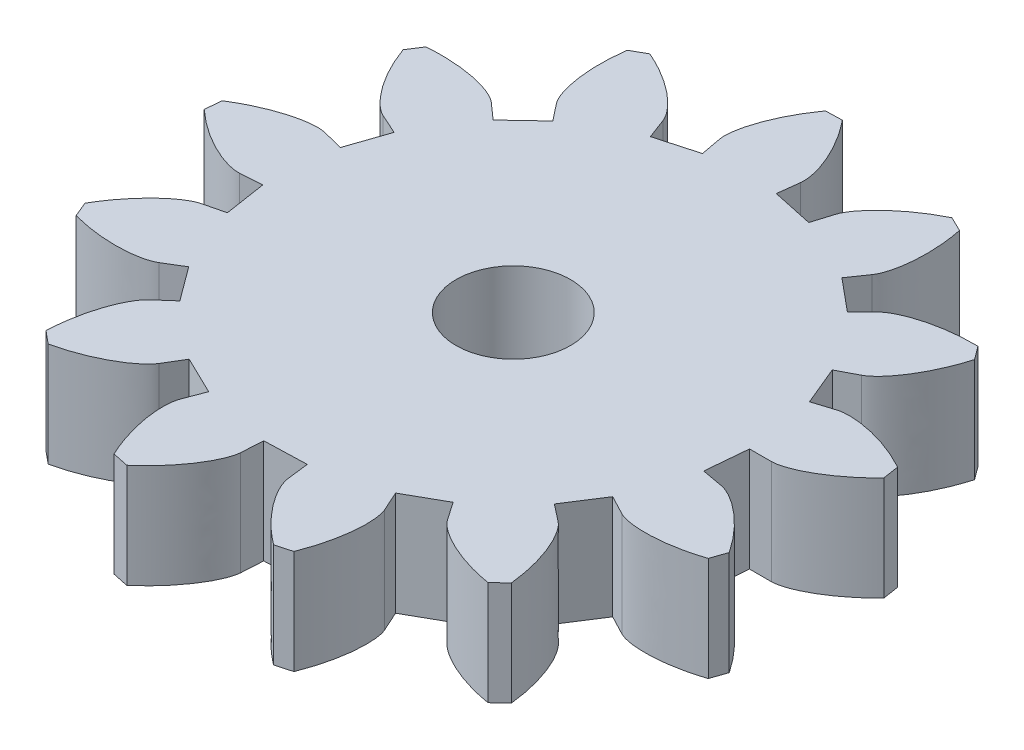
SolidWorks part; units mm, degrees
ref_plane "Front Plane" through (0, 0, 0) normal (0, 0, 1) x (1, 0, 0)
ref_plane "Top Plane" through (0, 0, 0) normal (0, 1, 0) x (1, 0, 0)
ref_plane "Right Plane" through (0, 0, 0) normal (1, 0, 0) x (0, 0, -1)
sketch "Sketch1" plane through (0, 0, 0) normal (0, 1, 0) x (1, 0, 0)
  circle A0 centre (0, 0) radius 8.2743 construction
  circle A1 centre (0, 0) radius 8.2743
sketch "Sketch2" plane through (0, 0, 0) normal (0, 1, 0) x (1, 0, 0)
  line L0 (6.8098, 0) -> (7.4374, 0)
  line L1 (7.4374, 0) -> (7.4435, 0.0002)
  line L2 (7.4435, 0.0002) -> (7.455, 0.0009)
  line L3 (7.455, 0.0009) -> (7.4719, 0.0023)
  line L4 (7.4719, 0.0023) -> (7.494, 0.0048)
  line L5 (7.494, 0.0048) -> (7.5213, 0.0086)
  line L6 (7.5213, 0.0086) -> (7.5538, 0.0141)
  line L7 (7.5538, 0.0141) -> (7.5915, 0.0214)
  line L8 (7.5915, 0.0214) -> (7.6341, 0.0309)
  line L9 (7.6341, 0.0309) -> (7.6817, 0.0428)
  line L10 (7.6817, 0.0428) -> (7.7341, 0.0575)
  line L11 (7.7341, 0.0575) -> (7.7912, 0.0751)
  line L12 (7.7912, 0.0751) -> (7.8529, 0.096)
  line L13 (7.8529, 0.096) -> (7.9191, 0.1204)
  line L14 (7.9191, 0.1204) -> (7.9895, 0.1486)
  line L15 (7.9895, 0.1486) -> (8.0641, 0.1807)
  line L16 (8.0641, 0.1807) -> (8.1427, 0.2171)
  line L17 (8.1427, 0.2171) -> (8.225, 0.258)
  line L18 (8.225, 0.258) -> (8.311, 0.3036)
  line L19 (8.311, 0.3036) -> (8.4004, 0.3541)
  line L20 (8.4004, 0.3541) -> (8.493, 0.4097)
  line L21 (8.493, 0.4097) -> (8.5886, 0.4707)
  line L22 (8.5886, 0.4707) -> (8.6869, 0.5373)
  line L23 (8.6869, 0.5373) -> (8.7878, 0.6095)
  line L24 (8.7878, 0.6095) -> (8.891, 0.6877)
  line L25 (8.891, 0.6877) -> (8.9962, 0.772)
  line L26 (8.9962, 0.772) -> (9.1033, 0.8626)
  line L27 (9.1033, 0.8626) -> (9.2118, 0.9596)
  line L28 (9.2118, 0.9596) -> (9.3216, 1.0631)
  line L29 (9.3216, 1.0631) -> (9.4324, 1.1733)
  line L30 (9.4324, 1.1733) -> (9.4602, 1.2019)
  line L31 (9.4602, 1.2019) -> (9.4672, 1.2092)
  line L32 (9.4672, 1.2092) -> (9.4689, 1.211)
  line L33 (9.4689, 1.211) -> (9.4692, 1.2112)
  line L34 (9.4692, 1.2112) -> (9.4693, 1.2114)
  line L35 (9.4693, 1.2114) -> (9.3971, 1.6821)
  line L36 (9.3971, 1.6821) -> (9.3969, 1.6823)
  line L37 (9.3969, 1.6823) -> (9.3966, 1.6825)
  line L38 (9.3966, 1.6825) -> (9.3944, 1.6837)
  line L39 (9.3944, 1.6837) -> (9.3856, 1.6885)
  line L40 (9.3856, 1.6885) -> (9.3505, 1.7074)
  line L41 (9.3505, 1.7074) -> (9.2118, 1.7794)
  line L42 (9.2118, 1.7794) -> (9.076, 1.8452)
  line L43 (9.076, 1.8452) -> (8.9434, 1.9052)
  line L44 (8.9434, 1.9052) -> (8.8141, 1.9595)
  line L45 (8.8141, 1.9595) -> (8.6884, 2.0084)
  line L46 (8.6884, 2.0084) -> (8.5666, 2.0521)
  line L47 (8.5666, 2.0521) -> (8.4487, 2.0908)
  line L48 (8.4487, 2.0908) -> (8.3349, 2.1248)
  line L49 (8.3349, 2.1248) -> (8.2254, 2.1544)
  line L50 (8.2254, 2.1544) -> (8.1204, 2.1797)
  line L51 (8.1204, 2.1797) -> (8.02, 2.2011)
  line L52 (8.02, 2.2011) -> (7.9243, 2.2189)
  line L53 (7.9243, 2.2189) -> (7.8335, 2.2332)
  line L54 (7.8335, 2.2332) -> (7.7476, 2.2443)
  line L55 (7.7476, 2.2443) -> (7.6668, 2.2527)
  line L56 (7.6668, 2.2527) -> (7.5912, 2.2584)
  line L57 (7.5912, 2.2584) -> (7.5207, 2.2618)
  line L58 (7.5207, 2.2618) -> (7.4556, 2.2633)
  line L59 (7.4556, 2.2633) -> (7.3958, 2.263)
  line L60 (7.3958, 2.263) -> (7.3415, 2.2613)
  line L61 (7.3415, 2.2613) -> (7.2925, 2.2584)
  line L62 (7.2925, 2.2584) -> (7.2489, 2.2547)
  line L63 (7.2489, 2.2547) -> (7.2109, 2.2504)
  line L64 (7.2109, 2.2504) -> (7.1782, 2.2458)
  line L65 (7.1782, 2.2458) -> (7.151, 2.2413)
  line L66 (7.151, 2.2413) -> (7.1291, 2.237)
  line L67 (7.1291, 2.237) -> (7.1126, 2.2334)
  line L68 (7.1126, 2.2334) -> (7.1015, 2.2306)
  line L69 (7.1015, 2.2306) -> (7.0955, 2.2289)
  line L70 (7.0955, 2.2289) -> (6.4968, 2.0408)
  line L71 (6.4968, 2.0408) -> (6.0298, 3.1647)
  line L72 (6.0298, 3.1647) -> (6.5855, 3.4563)
  line L73 (6.5855, 3.4563) -> (6.5908, 3.4594)
  line L74 (6.5908, 3.4594) -> (6.6007, 3.4653)
  line L75 (6.6007, 3.4653) -> (6.6149, 3.4744)
  line L76 (6.6149, 3.4744) -> (6.6333, 3.4869)
  line L77 (6.6333, 3.4869) -> (6.6558, 3.503)
  line L78 (6.6558, 3.503) -> (6.6821, 3.5229)
  line L79 (6.6821, 3.5229) -> (6.712, 3.5469)
  line L80 (6.712, 3.5469) -> (6.7453, 3.5751)
  line L81 (6.7453, 3.5751) -> (6.7819, 3.6078)
  line L82 (6.7819, 3.6078) -> (6.8215, 3.6451)
  line L83 (6.8215, 3.6451) -> (6.8639, 3.6873)
  line L84 (6.8639, 3.6873) -> (6.9088, 3.7345)
  line L85 (6.9088, 3.7345) -> (6.956, 3.7868)
  line L86 (6.956, 3.7868) -> (7.0053, 3.8445)
  line L87 (7.0053, 3.8445) -> (7.0564, 3.9076)
  line L88 (7.0564, 3.9076) -> (7.1091, 3.9763)
  line L89 (7.1091, 3.9763) -> (7.163, 4.0508)
  line L90 (7.163, 4.0508) -> (7.218, 4.1311)
  line L91 (7.218, 4.1311) -> (7.2736, 4.2174)
  line L92 (7.2736, 4.2174) -> (7.3298, 4.3097)
  line L93 (7.3298, 4.3097) -> (7.3861, 4.4081)
  line L94 (7.3861, 4.4081) -> (7.4422, 4.5127)
  line L95 (7.4422, 4.5127) -> (7.498, 4.6236)
  line L96 (7.498, 4.6236) -> (7.553, 4.7408)
  line L97 (7.553, 4.7408) -> (7.607, 4.8644)
  line L98 (7.607, 4.8644) -> (7.6597, 4.9943)
  line L99 (7.6597, 4.9943) -> (7.7107, 5.1306)
  line L100 (7.7107, 5.1306) -> (7.7598, 5.2733)
  line L101 (7.7598, 5.2733) -> (7.8067, 5.4224)
  line L102 (7.8067, 5.4224) -> (7.8181, 5.4607)
  line L103 (7.8181, 5.4607) -> (7.8209, 5.4703)
  line L104 (7.8209, 5.4703) -> (7.8216, 5.4727)
  line L105 (7.8216, 5.4727) -> (7.8217, 5.473)
  line L106 (7.8217, 5.473) -> (7.8216, 5.4732)
  line L107 (7.8216, 5.4732) -> (7.539, 5.8565)
  line L108 (7.539, 5.8565) -> (7.5387, 5.8566)
  line L109 (7.5387, 5.8566) -> (7.5384, 5.8566)
  line L110 (7.5384, 5.8566) -> (7.5359, 5.8566)
  line L111 (7.5359, 5.8566) -> (7.5259, 5.8568)
  line L112 (7.5259, 5.8568) -> (7.486, 5.8572)
  line L113 (7.486, 5.8572) -> (7.3297, 5.8565)
  line L114 (7.3297, 5.8565) -> (7.1789, 5.8517)
  line L115 (7.1789, 5.8517) -> (7.0336, 5.8432)
  line L116 (7.0336, 5.8432) -> (6.8939, 5.8312)
  line L117 (6.8939, 5.8312) -> (6.7599, 5.8161)
  line L118 (6.7599, 5.8161) -> (6.6317, 5.7981)
  line L119 (6.6317, 5.7981) -> (6.5093, 5.7776)
  line L120 (6.5093, 5.7776) -> (6.3927, 5.7549)
  line L121 (6.3927, 5.7549) -> (6.282, 5.7302)
  line L122 (6.282, 5.7302) -> (6.1773, 5.7038)
  line L123 (6.1773, 5.7038) -> (6.0784, 5.6761)
  line L124 (6.0784, 5.6761) -> (5.9855, 5.6473)
  line L125 (5.9855, 5.6473) -> (5.8984, 5.6178)
  line L126 (5.8984, 5.6178) -> (5.8172, 5.5878)
  line L127 (5.8172, 5.5878) -> (5.7418, 5.5576)
  line L128 (5.7418, 5.5576) -> (5.6721, 5.5275)
  line L129 (5.6721, 5.5275) -> (5.6082, 5.4978)
  line L130 (5.6082, 5.4978) -> (5.5498, 5.4688)
  line L131 (5.5498, 5.4688) -> (5.497, 5.4408)
  line L132 (5.497, 5.4408) -> (5.4497, 5.414)
  line L133 (5.4497, 5.414) -> (5.4076, 5.3887)
  line L134 (5.4076, 5.3887) -> (5.3708, 5.3652)
  line L135 (5.3708, 5.3652) -> (5.3391, 5.3437)
  line L136 (5.3391, 5.3437) -> (5.3123, 5.3245)
  line L137 (5.3123, 5.3245) -> (5.2903, 5.3078)
  line L138 (5.2903, 5.3078) -> (5.2729, 5.2939)
  line L139 (5.2729, 5.2939) -> (5.26, 5.283)
  line L140 (5.26, 5.283) -> (5.2514, 5.2753)
  line L141 (5.2514, 5.2753) -> (5.247, 5.2711)
  line L142 (5.247, 5.2711) -> (4.8042, 4.8263)
  line L143 (4.8042, 4.8263) -> (3.8684, 5.6043)
  line L144 (3.8684, 5.6043) -> (4.2249, 6.1208)
  line L145 (4.2249, 6.1208) -> (4.2282, 6.126)
  line L146 (4.2282, 6.126) -> (4.2342, 6.1359)
  line L147 (4.2342, 6.1359) -> (4.2426, 6.1505)
  line L148 (4.2426, 6.1505) -> (4.2531, 6.1702)
  line L149 (4.2531, 6.1702) -> (4.2655, 6.1948)
  line L150 (4.2655, 6.1948) -> (4.2795, 6.2247)
  line L151 (4.2795, 6.2247) -> (4.2948, 6.2598)
  line L152 (4.2948, 6.2598) -> (4.3112, 6.3003)
  line L153 (4.3112, 6.3003) -> (4.3284, 6.3462)
  line L154 (4.3284, 6.3462) -> (4.3462, 6.3977)
  line L155 (4.3462, 6.3977) -> (4.3641, 6.4547)
  line L156 (4.3641, 6.4547) -> (4.3819, 6.5174)
  line L157 (4.3819, 6.5174) -> (4.3994, 6.5857)
  line L158 (4.3994, 6.5857) -> (4.4163, 6.6596)
  line L159 (4.4163, 6.6596) -> (4.4322, 6.7393)
  line L160 (4.4322, 6.7393) -> (4.4469, 6.8246)
  line L161 (4.4469, 6.8246) -> (4.46, 6.9156)
  line L162 (4.46, 6.9156) -> (4.4714, 7.0123)
  line L163 (4.4714, 7.0123) -> (4.4806, 7.1145)
  line L164 (4.4806, 7.1145) -> (4.4874, 7.2223)
  line L165 (4.4874, 7.2223) -> (4.4915, 7.3356)
  line L166 (4.4915, 7.3356) -> (4.4926, 7.4544)
  line L167 (4.4926, 7.4544) -> (4.4904, 7.5785)
  line L168 (4.4904, 7.5785) -> (4.4847, 7.7078)
  line L169 (4.4847, 7.7078) -> (4.4751, 7.8423)
  line L170 (4.4751, 7.8423) -> (4.4613, 7.9819)
  line L171 (4.4613, 7.9819) -> (4.4432, 8.1263)
  line L172 (4.4432, 8.1263) -> (4.4204, 8.2755)
  line L173 (4.4204, 8.2755) -> (4.3926, 8.4293)
  line L174 (4.3926, 8.4293) -> (4.3849, 8.4684)
  line L175 (4.3849, 8.4684) -> (4.3829, 8.4782)
  line L176 (4.3829, 8.4782) -> (4.3824, 8.4807)
  line L177 (4.3824, 8.4807) -> (4.3823, 8.481)
  line L178 (4.3823, 8.481) -> (4.3822, 8.4812)
  line L179 (4.3822, 8.4812) -> (3.9538, 8.6892)
  line L180 (3.9538, 8.6892) -> (3.9535, 8.6892)
  line L181 (3.9535, 8.6892) -> (3.9533, 8.689)
  line L182 (3.9533, 8.689) -> (3.951, 8.6879)
  line L183 (3.951, 8.6879) -> (3.9421, 8.6834)
  line L184 (3.9421, 8.6834) -> (3.9065, 8.6652)
  line L185 (3.9065, 8.6652) -> (3.7685, 8.5919)
  line L186 (3.7685, 8.5919) -> (3.6371, 8.5176)
  line L187 (3.6371, 8.5176) -> (3.5125, 8.4425)
  line L188 (3.5125, 8.4425) -> (3.3943, 8.367)
  line L189 (3.3943, 8.367) -> (3.2827, 8.2914)
  line L190 (3.2827, 8.2914) -> (3.1775, 8.2159)
  line L191 (3.1775, 8.2159) -> (3.0787, 8.1408)
  line L192 (3.0787, 8.1408) -> (2.986, 8.0665)
  line L193 (2.986, 8.0665) -> (2.8995, 7.9932)
  line L194 (2.8995, 7.9932) -> (2.819, 7.9212)
  line L195 (2.819, 7.9212) -> (2.7444, 7.8507)
  line L196 (2.7444, 7.8507) -> (2.6754, 7.782)
  line L197 (2.6754, 7.782) -> (2.6121, 7.7154)
  line L198 (2.6121, 7.7154) -> (2.5541, 7.6511)
  line L199 (2.5541, 7.6511) -> (2.5013, 7.5893)
  line L200 (2.5013, 7.5893) -> (2.4537, 7.5303)
  line L201 (2.4537, 7.5303) -> (2.4108, 7.4743)
  line L202 (2.4108, 7.4743) -> (2.3726, 7.4215)
  line L203 (2.3726, 7.4215) -> (2.3389, 7.3722)
  line L204 (2.3389, 7.3722) -> (2.3094, 7.3265)
  line L205 (2.3094, 7.3265) -> (2.284, 7.2845)
  line L206 (2.284, 7.2845) -> (2.2623, 7.2466)
  line L207 (2.2623, 7.2466) -> (2.2442, 7.2128)
  line L208 (2.2442, 7.2128) -> (2.2294, 7.1833)
  line L209 (2.2294, 7.1833) -> (2.2177, 7.1583)
  line L210 (2.2177, 7.1583) -> (2.2088, 7.1379)
  line L211 (2.2088, 7.1379) -> (2.2024, 7.1223)
  line L212 (2.2024, 7.1223) -> (2.1984, 7.1115)
  line L213 (2.1984, 7.1115) -> (2.1964, 7.1057)
  line L214 (2.1964, 7.1057) -> (2.011, 6.5061)
  line L215 (2.011, 6.5061) -> (0.8208, 6.7601)
  line L216 (0.8208, 6.7601) -> (0.8965, 7.3831)
  line L217 (0.8965, 7.3831) -> (0.897, 7.3893)
  line L218 (0.897, 7.3893) -> (0.8977, 7.4008)
  line L219 (0.8977, 7.4008) -> (0.8983, 7.4177)
  line L220 (0.8983, 7.4177) -> (0.8985, 7.4399)
  line L221 (0.8985, 7.4399) -> (0.898, 7.4675)
  line L222 (0.898, 7.4675) -> (0.8965, 7.5005)
  line L223 (0.8965, 7.5005) -> (0.8938, 7.5387)
  line L224 (0.8938, 7.5387) -> (0.8895, 7.5822)
  line L225 (0.8895, 7.5822) -> (0.8834, 7.6309)
  line L226 (0.8834, 7.6309) -> (0.8752, 7.6846)
  line L227 (0.8752, 7.6846) -> (0.8645, 7.7435)
  line L228 (0.8645, 7.7435) -> (0.8512, 7.8072)
  line L229 (0.8512, 7.8072) -> (0.835, 7.8758)
  line L230 (0.835, 7.8758) -> (0.8156, 7.9492)
  line L231 (0.8156, 7.9492) -> (0.7926, 8.0271)
  line L232 (0.7926, 8.0271) -> (0.766, 8.1095)
  line L233 (0.766, 8.1095) -> (0.7353, 8.1962)
  line L234 (0.7353, 8.1962) -> (0.7004, 8.287)
  line L235 (0.7004, 8.287) -> (0.6611, 8.3818)
  line L236 (0.6611, 8.3818) -> (0.617, 8.4804)
  line L237 (0.617, 8.4804) -> (0.568, 8.5827)
  line L238 (0.568, 8.5827) -> (0.5138, 8.6883)
  line L239 (0.5138, 8.6883) -> (0.4542, 8.7972)
  line L240 (0.4542, 8.7972) -> (0.389, 8.9091)
  line L241 (0.389, 8.9091) -> (0.318, 9.0237)
  line L242 (0.318, 9.0237) -> (0.241, 9.1409)
  line L243 (0.241, 9.1409) -> (0.1578, 9.2603)
  line L244 (0.1578, 9.2603) -> (0.0682, 9.3818)
  line L245 (0.0682, 9.3818) -> (-0.0278, 9.5051)
  line L246 (-0.0278, 9.5051) -> (-0.0529, 9.5361)
  line L247 (-0.0529, 9.5361) -> (-0.0592, 9.5439)
  line L248 (-0.0592, 9.5439) -> (-0.0608, 9.5459)
  line L249 (-0.0608, 9.5459) -> (-0.061, 9.5461)
  line L250 (-0.061, 9.5461) -> (-0.0612, 9.5462)
  line L251 (-0.0612, 9.5462) -> (-0.5372, 9.5313)
  line L252 (-0.5372, 9.5313) -> (-0.5374, 9.5312)
  line L253 (-0.5374, 9.5312) -> (-0.5375, 9.5309)
  line L254 (-0.5375, 9.5309) -> (-0.539, 9.5289)
  line L255 (-0.539, 9.5289) -> (-0.5448, 9.5207)
  line L256 (-0.5448, 9.5207) -> (-0.5679, 9.4881)
  line L257 (-0.5679, 9.4881) -> (-0.656, 9.3591)
  line L258 (-0.656, 9.3591) -> (-0.7378, 9.2322)
  line L259 (-0.7378, 9.2322) -> (-0.8133, 9.1078)
  line L260 (-0.8133, 9.1078) -> (-0.8828, 8.986)
  line L261 (-0.8828, 8.986) -> (-0.9465, 8.8672)
  line L262 (-0.9465, 8.8672) -> (-1.0046, 8.7515)
  line L263 (-1.0046, 8.7515) -> (-1.0572, 8.6391)
  line L264 (-1.0572, 8.6391) -> (-1.1047, 8.5302)
  line L265 (-1.1047, 8.5302) -> (-1.1472, 8.4251)
  line L266 (-1.1472, 8.4251) -> (-1.185, 8.3239)
  line L267 (-1.185, 8.3239) -> (-1.2184, 8.2268)
  line L268 (-1.2184, 8.2268) -> (-1.2475, 8.134)
  line L269 (-1.2475, 8.134) -> (-1.2727, 8.0455)
  line L270 (-1.2727, 8.0455) -> (-1.2941, 7.9616)
  line L271 (-1.2941, 7.9616) -> (-1.3121, 7.8824)
  line L272 (-1.3121, 7.8824) -> (-1.3269, 7.808)
  line L273 (-1.3269, 7.808) -> (-1.3388, 7.7385)
  line L274 (-1.3388, 7.7385) -> (-1.3481, 7.6741)
  line L275 (-1.3481, 7.6741) -> (-1.355, 7.6147)
  line L276 (-1.355, 7.6147) -> (-1.3599, 7.5605)
  line L277 (-1.3599, 7.5605) -> (-1.3629, 7.5115)
  line L278 (-1.3629, 7.5115) -> (-1.3645, 7.4679)
  line L279 (-1.3645, 7.4679) -> (-1.3648, 7.4295)
  line L280 (-1.3648, 7.4295) -> (-1.3642, 7.3966)
  line L281 (-1.3642, 7.3966) -> (-1.363, 7.369)
  line L282 (-1.363, 7.369) -> (-1.3614, 7.3468)
  line L283 (-1.3614, 7.3468) -> (-1.3597, 7.33)
  line L284 (-1.3597, 7.33) -> (-1.3583, 7.3186)
  line L285 (-1.3583, 7.3186) -> (-1.3574, 7.3125)
  line L286 (-1.3574, 7.3125) -> (-1.2429, 6.6954)
  line L287 (-1.2429, 6.6954) -> (-2.4148, 6.3673)
  line L288 (-2.4148, 6.3673) -> (-2.6373, 6.9541)
  line L289 (-2.6373, 6.9541) -> (-2.6397, 6.9598)
  line L290 (-2.6397, 6.9598) -> (-2.6444, 6.9703)
  line L291 (-2.6444, 6.9703) -> (-2.6517, 6.9855)
  line L292 (-2.6517, 6.9855) -> (-2.6619, 7.0053)
  line L293 (-2.6619, 7.0053) -> (-2.6752, 7.0295)
  line L294 (-2.6752, 7.0295) -> (-2.6918, 7.058)
  line L295 (-2.6918, 7.058) -> (-2.712, 7.0906)
  line L296 (-2.712, 7.0906) -> (-2.736, 7.1271)
  line L297 (-2.736, 7.1271) -> (-2.764, 7.1673)
  line L298 (-2.764, 7.1673) -> (-2.7963, 7.2111)
  line L299 (-2.7963, 7.2111) -> (-2.8331, 7.2583)
  line L300 (-2.8331, 7.2583) -> (-2.8745, 7.3086)
  line L301 (-2.8745, 7.3086) -> (-2.9207, 7.3618)
  line L302 (-2.9207, 7.3618) -> (-2.972, 7.4176)
  line L303 (-2.972, 7.4176) -> (-3.0285, 7.476)
  line L304 (-3.0285, 7.476) -> (-3.0904, 7.5365)
  line L305 (-3.0904, 7.5365) -> (-3.1578, 7.5991)
  line L306 (-3.1578, 7.5991) -> (-3.2309, 7.6633)
  line L307 (-3.2309, 7.6633) -> (-3.3099, 7.729)
  line L308 (-3.3099, 7.729) -> (-3.3947, 7.7958)
  line L309 (-3.3947, 7.7958) -> (-3.4857, 7.8635)
  line L310 (-3.4857, 7.8635) -> (-3.5828, 7.9319)
  line L311 (-3.5828, 7.9319) -> (-3.6861, 8.0006)
  line L312 (-3.6861, 8.0006) -> (-3.7958, 8.0694)
  line L313 (-3.7958, 8.0694) -> (-3.912, 8.1379)
  line L314 (-3.912, 8.1379) -> (-4.0346, 8.2058)
  line L315 (-4.0346, 8.2058) -> (-4.1638, 8.2729)
  line L316 (-4.1638, 8.2729) -> (-4.2995, 8.3389)
  line L317 (-4.2995, 8.3389) -> (-4.4419, 8.4034)
  line L318 (-4.4419, 8.4034) -> (-4.4785, 8.4193)
  line L319 (-4.4785, 8.4193) -> (-4.4877, 8.4232)
  line L320 (-4.4877, 8.4232) -> (-4.49, 8.4242)
  line L321 (-4.49, 8.4242) -> (-4.4903, 8.4243)
  line L322 (-4.4903, 8.4243) -> (-4.4905, 8.4243)
  line L323 (-4.4905, 8.4243) -> (-4.9051, 8.1899)
  line L324 (-4.9051, 8.1899) -> (-4.9052, 8.1897)
  line L325 (-4.9052, 8.1897) -> (-4.9052, 8.1894)
  line L326 (-4.9052, 8.1894) -> (-4.9056, 8.1869)
  line L327 (-4.9056, 8.1869) -> (-4.9069, 8.177)
  line L328 (-4.9069, 8.177) -> (-4.9122, 8.1374)
  line L329 (-4.9122, 8.1374) -> (-4.9303, 7.9822)
  line L330 (-4.9303, 7.9822) -> (-4.9437, 7.8319)
  line L331 (-4.9437, 7.8319) -> (-4.9528, 7.6866)
  line L332 (-4.9528, 7.6866) -> (-4.9577, 7.5465)
  line L333 (-4.9577, 7.5465) -> (-4.9589, 7.4116)
  line L334 (-4.9589, 7.4116) -> (-4.9565, 7.2822)
  line L335 (-4.9565, 7.2822) -> (-4.9509, 7.1582)
  line L336 (-4.9509, 7.1582) -> (-4.9424, 7.0398)
  line L337 (-4.9424, 7.0398) -> (-4.9312, 6.9269)
  line L338 (-4.9312, 6.9269) -> (-4.9176, 6.8197)
  line L339 (-4.9176, 6.8197) -> (-4.902, 6.7183)
  line L340 (-4.902, 6.7183) -> (-4.8847, 6.6225)
  line L341 (-4.8847, 6.6225) -> (-4.8658, 6.5325)
  line L342 (-4.8658, 6.5325) -> (-4.8458, 6.4483)
  line L343 (-4.8458, 6.4483) -> (-4.825, 6.3698)
  line L344 (-4.825, 6.3698) -> (-4.8035, 6.297)
  line L345 (-4.8035, 6.297) -> (-4.7818, 6.23)
  line L346 (-4.7818, 6.23) -> (-4.76, 6.1686)
  line L347 (-4.76, 6.1686) -> (-4.7385, 6.1128)
  line L348 (-4.7385, 6.1128) -> (-4.7176, 6.0625)
  line L349 (-4.7176, 6.0625) -> (-4.6976, 6.0177)
  line L350 (-4.6976, 6.0177) -> (-4.6787, 5.9784)
  line L351 (-4.6787, 5.9784) -> (-4.6612, 5.9443)
  line L352 (-4.6612, 5.9443) -> (-4.6453, 5.9154)
  line L353 (-4.6453, 5.9154) -> (-4.6314, 5.8915)
  line L354 (-4.6314, 5.8915) -> (-4.6197, 5.8726)
  line L355 (-4.6197, 5.8726) -> (-4.6104, 5.8585)
  line L356 (-4.6104, 5.8585) -> (-4.6038, 5.849)
  line L357 (-4.6038, 5.849) -> (-4.6002, 5.8441)
  line L358 (-4.6002, 5.8441) -> (-4.212, 5.3509)
  line L359 (-4.212, 5.3509) -> (-5.0972, 4.5157)
  line L360 (-5.0972, 4.5157) -> (-5.567, 4.9319)
  line L361 (-5.567, 4.9319) -> (-5.5717, 4.9358)
  line L362 (-5.5717, 4.9358) -> (-5.5808, 4.9429)
  line L363 (-5.5808, 4.9429) -> (-5.5943, 4.953)
  line L364 (-5.5943, 4.953) -> (-5.6125, 4.9658)
  line L365 (-5.6125, 4.9658) -> (-5.6355, 4.9811)
  line L366 (-5.6355, 4.9811) -> (-5.6635, 4.9986)
  line L367 (-5.6635, 4.9986) -> (-5.6965, 5.0181)
  line L368 (-5.6965, 5.0181) -> (-5.7347, 5.0392)
  line L369 (-5.7347, 5.0392) -> (-5.7782, 5.0618)
  line L370 (-5.7782, 5.0618) -> (-5.8272, 5.0856)
  line L371 (-5.8272, 5.0856) -> (-5.8816, 5.1103)
  line L372 (-5.8816, 5.1103) -> (-5.9417, 5.1356)
  line L373 (-5.9417, 5.1356) -> (-6.0074, 5.1612)
  line L374 (-6.0074, 5.1612) -> (-6.0787, 5.1868)
  line L375 (-6.0787, 5.1868) -> (-6.1559, 5.2122)
  line L376 (-6.1559, 5.2122) -> (-6.2388, 5.2371)
  line L377 (-6.2388, 5.2371) -> (-6.3276, 5.2611)
  line L378 (-6.3276, 5.2611) -> (-6.4222, 5.284)
  line L379 (-6.4222, 5.284) -> (-6.5226, 5.3055)
  line L380 (-6.5226, 5.3055) -> (-6.6288, 5.3252)
  line L381 (-6.6288, 5.3252) -> (-6.7408, 5.3429)
  line L382 (-6.7408, 5.3429) -> (-6.8585, 5.3584)
  line L383 (-6.8585, 5.3584) -> (-6.982, 5.3712)
  line L384 (-6.982, 5.3712) -> (-7.1111, 5.381)
  line L385 (-7.1111, 5.381) -> (-7.2457, 5.3877)
  line L386 (-7.2457, 5.3877) -> (-7.3859, 5.3909)
  line L387 (-7.3859, 5.3909) -> (-7.5315, 5.3903)
  line L388 (-7.5315, 5.3903) -> (-7.6823, 5.3856)
  line L389 (-7.6823, 5.3856) -> (-7.8383, 5.3766)
  line L390 (-7.8383, 5.3766) -> (-7.8781, 5.3736)
  line L391 (-7.8781, 5.3736) -> (-7.8881, 5.3729)
  line L392 (-7.8881, 5.3729) -> (-7.8906, 5.3727)
  line L393 (-7.8906, 5.3727) -> (-7.8909, 5.3726)
  line L394 (-7.8909, 5.3726) -> (-7.8912, 5.3725)
  line L395 (-7.8912, 5.3725) -> (-8.1493, 4.9723)
  line L396 (-8.1493, 4.9723) -> (-8.1493, 4.9721)
  line L397 (-8.1493, 4.9721) -> (-8.1492, 4.9718)
  line L398 (-8.1492, 4.9718) -> (-8.1483, 4.9694)
  line L399 (-8.1483, 4.9694) -> (-8.1449, 4.96)
  line L400 (-8.1449, 4.96) -> (-8.1312, 4.9225)
  line L401 (-8.1312, 4.9225) -> (-8.0751, 4.7767)
  line L402 (-8.0751, 4.7767) -> (-8.0171, 4.6373)
  line L403 (-8.0171, 4.6373) -> (-7.9576, 4.5045)
  line L404 (-7.9576, 4.5045) -> (-7.8969, 4.3781)
  line L405 (-7.8969, 4.3781) -> (-7.8352, 4.2582)
  line L406 (-7.8352, 4.2582) -> (-7.773, 4.1447)
  line L407 (-7.773, 4.1447) -> (-7.7104, 4.0375)
  line L408 (-7.7104, 4.0375) -> (-7.6478, 3.9366)
  line L409 (-7.6478, 3.9366) -> (-7.5854, 3.8419)
  line L410 (-7.5854, 3.8419) -> (-7.5236, 3.7533)
  line L411 (-7.5236, 3.7533) -> (-7.4627, 3.6707)
  line L412 (-7.4627, 3.6707) -> (-7.4028, 3.5939)
  line L413 (-7.4028, 3.5939) -> (-7.3443, 3.523)
  line L414 (-7.3443, 3.523) -> (-7.2874, 3.4577)
  line L415 (-7.2874, 3.4577) -> (-7.2325, 3.3979)
  line L416 (-7.2325, 3.3979) -> (-7.1797, 3.3434)
  line L417 (-7.1797, 3.3434) -> (-7.1292, 3.2942)
  line L418 (-7.1292, 3.2942) -> (-7.0814, 3.2499)
  line L419 (-7.0814, 3.2499) -> (-7.0365, 3.2105)
  line L420 (-7.0365, 3.2105) -> (-6.9947, 3.1757)
  line L421 (-6.9947, 3.1757) -> (-6.9561, 3.1454)
  line L422 (-6.9561, 3.1454) -> (-6.9211, 3.1193)
  line L423 (-6.9211, 3.1193) -> (-6.8897, 3.0972)
  line L424 (-6.8897, 3.0972) -> (-6.8622, 3.079)
  line L425 (-6.8622, 3.079) -> (-6.8388, 3.0643)
  line L426 (-6.8388, 3.0643) -> (-6.8197, 3.0531)
  line L427 (-6.8197, 3.0531) -> (-6.8049, 3.0449)
  line L428 (-6.8049, 3.0449) -> (-6.7947, 3.0395)
  line L429 (-6.7947, 3.0395) -> (-6.7891, 3.0368)
  line L430 (-6.7891, 3.0368) -> (-6.2162, 2.7806)
  line L431 (-6.2162, 2.7806) -> (-6.6119, 1.6297)
  line L432 (-6.6119, 1.6297) -> (-7.2213, 1.7799)
  line L433 (-7.2213, 1.7799) -> (-7.2273, 1.7811)
  line L434 (-7.2273, 1.7811) -> (-7.2386, 1.7832)
  line L435 (-7.2386, 1.7832) -> (-7.2553, 1.7859)
  line L436 (-7.2553, 1.7859) -> (-7.2774, 1.7887)
  line L437 (-7.2774, 1.7887) -> (-7.3048, 1.7916)
  line L438 (-7.3048, 1.7916) -> (-7.3377, 1.7941)
  line L439 (-7.3377, 1.7941) -> (-7.376, 1.796)
  line L440 (-7.376, 1.796) -> (-7.4197, 1.797)
  line L441 (-7.4197, 1.797) -> (-7.4687, 1.7968)
  line L442 (-7.4687, 1.7968) -> (-7.5231, 1.7951)
  line L443 (-7.5231, 1.7951) -> (-7.5828, 1.7916)
  line L444 (-7.5828, 1.7916) -> (-7.6477, 1.7861)
  line L445 (-7.6477, 1.7861) -> (-7.7178, 1.7782)
  line L446 (-7.7178, 1.7782) -> (-7.7929, 1.7678)
  line L447 (-7.7929, 1.7678) -> (-7.873, 1.7544)
  line L448 (-7.873, 1.7544) -> (-7.958, 1.7379)
  line L449 (-7.958, 1.7379) -> (-8.0478, 1.7179)
  line L450 (-8.0478, 1.7179) -> (-8.1421, 1.6942)
  line L451 (-8.1421, 1.6942) -> (-8.241, 1.6666)
  line L452 (-8.241, 1.6666) -> (-8.3442, 1.6347)
  line L453 (-8.3442, 1.6347) -> (-8.4517, 1.5984)
  line L454 (-8.4517, 1.5984) -> (-8.5631, 1.5573)
  line L455 (-8.5631, 1.5573) -> (-8.6783, 1.5112)
  line L456 (-8.6783, 1.5112) -> (-8.7972, 1.46)
  line L457 (-8.7972, 1.46) -> (-8.9196, 1.4033)
  line L458 (-8.9196, 1.4033) -> (-9.0452, 1.341)
  line L459 (-9.0452, 1.341) -> (-9.1738, 1.2728)
  line L460 (-9.1738, 1.2728) -> (-9.3052, 1.1986)
  line L461 (-9.3052, 1.1986) -> (-9.4391, 1.1181)
  line L462 (-9.4391, 1.1181) -> (-9.473, 1.097)
  line L463 (-9.473, 1.097) -> (-9.4815, 1.0916)
  line L464 (-9.4815, 1.0916) -> (-9.4836, 1.0903)
  line L465 (-9.4836, 1.0903) -> (-9.4839, 1.0901)
  line L466 (-9.4839, 1.0901) -> (-9.484, 1.0899)
  line L467 (-9.484, 1.0899) -> (-9.5266, 0.6156)
  line L468 (-9.5266, 0.6156) -> (-9.5265, 0.6154)
  line L469 (-9.5265, 0.6154) -> (-9.5262, 0.6152)
  line L470 (-9.5262, 0.6152) -> (-9.5244, 0.6135)
  line L471 (-9.5244, 0.6135) -> (-9.517, 0.6067)
  line L472 (-9.517, 0.6067) -> (-9.4874, 0.5799)
  line L473 (-9.4874, 0.5799) -> (-9.3699, 0.4769)
  line L474 (-9.3699, 0.4769) -> (-9.2538, 0.3804)
  line L475 (-9.2538, 0.3804) -> (-9.1394, 0.2904)
  line L476 (-9.1394, 0.2904) -> (-9.0269, 0.2068)
  line L477 (-9.0269, 0.2068) -> (-8.9166, 0.1292)
  line L478 (-8.9166, 0.1292) -> (-8.8087, 0.0576)
  line L479 (-8.8087, 0.0576) -> (-8.7035, -0.0082)
  line L480 (-8.7035, -0.0082) -> (-8.6012, -0.0684)
  line L481 (-8.6012, -0.0684) -> (-8.502, -0.1233)
  line L482 (-8.502, -0.1233) -> (-8.4061, -0.1731)
  line L483 (-8.4061, -0.1731) -> (-8.3137, -0.2179)
  line L484 (-8.3137, -0.2179) -> (-8.225, -0.258)
  line L485 (-8.225, -0.258) -> (-8.1403, -0.2936)
  line L486 (-8.1403, -0.2936) -> (-8.0596, -0.325)
  line L487 (-8.0596, -0.325) -> (-7.9831, -0.3524)
  line L488 (-7.9831, -0.3524) -> (-7.911, -0.3761)
  line L489 (-7.911, -0.3761) -> (-7.8435, -0.3963)
  line L490 (-7.8435, -0.3963) -> (-7.7806, -0.4133)
  line L491 (-7.7806, -0.4133) -> (-7.7225, -0.4273)
  line L492 (-7.7225, -0.4273) -> (-7.6693, -0.4386)
  line L493 (-7.6693, -0.4386) -> (-7.6211, -0.4476)
  line L494 (-7.6211, -0.4476) -> (-7.5779, -0.4544)
  line L495 (-7.5779, -0.4544) -> (-7.5399, -0.4593)
  line L496 (-7.5399, -0.4593) -> (-7.5071, -0.4627)
  line L497 (-7.5071, -0.4627) -> (-7.4795, -0.4648)
  line L498 (-7.4795, -0.4648) -> (-7.4573, -0.4659)
  line L499 (-7.4573, -0.4659) -> (-7.4404, -0.4663)
  line L500 (-7.4404, -0.4663) -> (-7.4289, -0.4662)
  line L501 (-7.4289, -0.4662) -> (-7.4228, -0.4661)
  line L502 (-7.4228, -0.4661) -> (-6.7964, -0.4267)
  line L503 (-6.7964, -0.4267) -> (-6.6119, -1.6297)
  line L504 (-6.6119, -1.6297) -> (-7.2213, -1.7799)
  line L505 (-7.2213, -1.7799) -> (-7.2272, -1.7816)
  line L506 (-7.2272, -1.7816) -> (-7.2382, -1.785)
  line L507 (-7.2382, -1.785) -> (-7.2542, -1.7904)
  line L508 (-7.2542, -1.7904) -> (-7.2751, -1.7981)
  line L509 (-7.2751, -1.7981) -> (-7.3007, -1.8084)
  line L510 (-7.3007, -1.8084) -> (-7.331, -1.8214)
  line L511 (-7.331, -1.8214) -> (-7.3658, -1.8375)
  line L512 (-7.3658, -1.8375) -> (-7.4049, -1.857)
  line L513 (-7.4049, -1.857) -> (-7.4482, -1.8799)
  line L514 (-7.4482, -1.8799) -> (-7.4956, -1.9067)
  line L515 (-7.4956, -1.9067) -> (-7.5468, -1.9375)
  line L516 (-7.5468, -1.9375) -> (-7.6017, -1.9726)
  line L517 (-7.6017, -1.9726) -> (-7.6601, -2.0121)
  line L518 (-7.6601, -2.0121) -> (-7.7218, -2.0563)
  line L519 (-7.7218, -2.0563) -> (-7.7865, -2.1053)
  line L520 (-7.7865, -2.1053) -> (-7.8541, -2.1595)
  line L521 (-7.8541, -2.1595) -> (-7.9243, -2.2189)
  line L522 (-7.9243, -2.2189) -> (-7.9969, -2.2837)
  line L523 (-7.9969, -2.2837) -> (-8.0716, -2.3541)
  line L524 (-8.0716, -2.3541) -> (-8.1481, -2.4303)
  line L525 (-8.1481, -2.4303) -> (-8.2264, -2.5124)
  line L526 (-8.2264, -2.5124) -> (-8.3059, -2.6006)
  line L527 (-8.3059, -2.6006) -> (-8.3866, -2.6949)
  line L528 (-8.3866, -2.6949) -> (-8.4681, -2.7955)
  line L529 (-8.4681, -2.7955) -> (-8.5501, -2.9026)
  line L530 (-8.5501, -2.9026) -> (-8.6323, -3.0161)
  line L531 (-8.6323, -3.0161) -> (-8.7145, -3.1362)
  line L532 (-8.7145, -3.1362) -> (-8.7963, -3.263)
  line L533 (-8.7963, -3.263) -> (-8.8775, -3.3966)
  line L534 (-8.8775, -3.3966) -> (-8.8977, -3.431)
  line L535 (-8.8977, -3.431) -> (-8.9027, -3.4397)
  line L536 (-8.9027, -3.4397) -> (-8.904, -3.4418)
  line L537 (-8.904, -3.4418) -> (-8.9041, -3.4421)
  line L538 (-8.9041, -3.4421) -> (-8.9042, -3.4423)
  line L539 (-8.9042, -3.4423) -> (-8.7214, -3.8821)
  line L540 (-8.7214, -3.8821) -> (-8.7213, -3.8822)
  line L541 (-8.7213, -3.8822) -> (-8.7209, -3.8823)
  line L542 (-8.7209, -3.8823) -> (-8.7185, -3.883)
  line L543 (-8.7185, -3.883) -> (-8.7088, -3.8855)
  line L544 (-8.7088, -3.8855) -> (-8.6702, -3.8955)
  line L545 (-8.6702, -3.8955) -> (-8.5183, -3.9322)
  line L546 (-8.5183, -3.9322) -> (-8.3707, -3.9636)
  line L547 (-8.3707, -3.9636) -> (-8.2275, -3.9901)
  line L548 (-8.2275, -3.9901) -> (-8.089, -4.0119)
  line L549 (-8.089, -4.0119) -> (-7.9553, -4.0293)
  line L550 (-7.9553, -4.0293) -> (-7.8265, -4.0426)
  line L551 (-7.8265, -4.0426) -> (-7.7028, -4.052)
  line L552 (-7.7028, -4.052) -> (-7.5842, -4.0578)
  line L553 (-7.5842, -4.0578) -> (-7.4708, -4.0603)
  line L554 (-7.4708, -4.0603) -> (-7.3628, -4.0597)
  line L555 (-7.3628, -4.0597) -> (-7.2602, -4.0565)
  line L556 (-7.2602, -4.0565) -> (-7.163, -4.0508)
  line L557 (-7.163, -4.0508) -> (-7.0714, -4.0429)
  line L558 (-7.0714, -4.0429) -> (-6.9854, -4.0332)
  line L559 (-6.9854, -4.0332) -> (-6.9049, -4.022)
  line L560 (-6.9049, -4.022) -> (-6.8301, -4.0095)
  line L561 (-6.8301, -4.0095) -> (-6.7609, -3.9959)
  line L562 (-6.7609, -3.9959) -> (-6.6973, -3.9818)
  line L563 (-6.6973, -3.9818) -> (-6.6394, -3.9672)
  line L564 (-6.6394, -3.9672) -> (-6.587, -3.9525)
  line L565 (-6.587, -3.9525) -> (-6.5401, -3.938)
  line L566 (-6.5401, -3.938) -> (-6.4987, -3.924)
  line L567 (-6.4987, -3.924) -> (-6.4628, -3.9107)
  line L568 (-6.4628, -3.9107) -> (-6.4322, -3.8984)
  line L569 (-6.4322, -3.8984) -> (-6.4068, -3.8875)
  line L570 (-6.4068, -3.8875) -> (-6.3866, -3.8781)
  line L571 (-6.3866, -3.8781) -> (-6.3715, -3.8706)
  line L572 (-6.3715, -3.8706) -> (-6.3613, -3.8652)
  line L573 (-6.3613, -3.8652) -> (-6.3559, -3.8622)
  line L574 (-6.3559, -3.8622) -> (-5.8196, -3.5363)
  line L575 (-5.8196, -3.5363) -> (-5.0972, -4.5157)
  line L576 (-5.0972, -4.5157) -> (-5.5669, -4.9319)
  line L577 (-5.5669, -4.9319) -> (-5.5714, -4.9361)
  line L578 (-5.5714, -4.9361) -> (-5.5796, -4.9443)
  line L579 (-5.5796, -4.9443) -> (-5.5912, -4.9565)
  line L580 (-5.5912, -4.9565) -> (-5.6061, -4.973)
  line L581 (-5.6061, -4.973) -> (-5.6241, -4.994)
  line L582 (-5.6241, -4.994) -> (-5.6448, -5.0197)
  line L583 (-5.6448, -5.0197) -> (-5.6681, -5.0501)
  line L584 (-5.6681, -5.0501) -> (-5.6937, -5.0855)
  line L585 (-5.6937, -5.0855) -> (-5.7214, -5.126)
  line L586 (-5.7214, -5.126) -> (-5.7509, -5.1717)
  line L587 (-5.7509, -5.1717) -> (-5.782, -5.2228)
  line L588 (-5.782, -5.2228) -> (-5.8143, -5.2793)
  line L589 (-5.8143, -5.2793) -> (-5.8477, -5.3414)
  line L590 (-5.8477, -5.3414) -> (-5.8817, -5.4092)
  line L591 (-5.8817, -5.4092) -> (-5.9162, -5.4828)
  line L592 (-5.9162, -5.4828) -> (-5.9509, -5.5621)
  line L593 (-5.9509, -5.5621) -> (-5.9855, -5.6473)
  line L594 (-5.9855, -5.6473) -> (-6.0196, -5.7384)
  line L595 (-6.0196, -5.7384) -> (-6.053, -5.8355)
  line L596 (-6.053, -5.8355) -> (-6.0854, -5.9386)
  line L597 (-6.0854, -5.9386) -> (-6.1165, -6.0476)
  line L598 (-6.1165, -6.0476) -> (-6.146, -6.1626)
  line L599 (-6.146, -6.1626) -> (-6.1736, -6.2836)
  line L600 (-6.1736, -6.2836) -> (-6.1989, -6.4106)
  line L601 (-6.1989, -6.4106) -> (-6.2218, -6.5435)
  line L602 (-6.2218, -6.5435) -> (-6.2419, -6.6822)
  line L603 (-6.2419, -6.6822) -> (-6.2588, -6.8268)
  line L604 (-6.2588, -6.8268) -> (-6.2724, -6.9771)
  line L605 (-6.2724, -6.9771) -> (-6.2822, -7.1331)
  line L606 (-6.2822, -7.1331) -> (-6.2841, -7.173)
  line L607 (-6.2841, -7.173) -> (-6.2845, -7.183)
  line L608 (-6.2845, -7.183) -> (-6.2846, -7.1855)
  line L609 (-6.2846, -7.1855) -> (-6.2846, -7.1858)
  line L610 (-6.2846, -7.1858) -> (-6.2845, -7.186)
  line L611 (-6.2845, -7.186) -> (-5.9183, -7.4905)
  line L612 (-5.9183, -7.4905) -> (-5.9181, -7.4905)
  line L613 (-5.9181, -7.4905) -> (-5.9178, -7.4905)
  line L614 (-5.9178, -7.4905) -> (-5.9154, -7.4899)
  line L615 (-5.9154, -7.4899) -> (-5.9056, -7.4877)
  line L616 (-5.9056, -7.4877) -> (-5.8667, -7.4786)
  line L617 (-5.8667, -7.4786) -> (-5.7152, -7.4404)
  line L618 (-5.7152, -7.4404) -> (-5.5699, -7.3997)
  line L619 (-5.5699, -7.3997) -> (-5.4308, -7.3566)
  line L620 (-5.4308, -7.3566) -> (-5.298, -7.3116)
  line L621 (-5.298, -7.3116) -> (-5.1716, -7.2648)
  line L622 (-5.1716, -7.2648) -> (-5.0514, -7.2167)
  line L623 (-5.0514, -7.2167) -> (-4.9374, -7.1675)
  line L624 (-4.9374, -7.1675) -> (-4.8297, -7.1175)
  line L625 (-4.8297, -7.1175) -> (-4.7282, -7.067)
  line L626 (-4.7282, -7.067) -> (-4.6328, -7.0164)
  line L627 (-4.6328, -7.0164) -> (-4.5434, -6.9658)
  line L628 (-4.5434, -6.9658) -> (-4.46, -6.9156)
  line L629 (-4.46, -6.9156) -> (-4.3826, -6.8661)
  line L630 (-4.3826, -6.8661) -> (-4.3109, -6.8175)
  line L631 (-4.3109, -6.8175) -> (-4.2449, -6.7702)
  line L632 (-4.2449, -6.7702) -> (-4.1845, -6.7243)
  line L633 (-4.1845, -6.7243) -> (-4.1295, -6.6802)
  line L634 (-4.1295, -6.6802) -> (-4.0798, -6.6381)
  line L635 (-4.0798, -6.6381) -> (-4.0352, -6.5982)
  line L636 (-4.0352, -6.5982) -> (-3.9957, -6.5609)
  line L637 (-3.9957, -6.5609) -> (-3.9609, -6.5263)
  line L638 (-3.9609, -6.5263) -> (-3.9308, -6.4946)
  line L639 (-3.9308, -6.4946) -> (-3.9051, -6.4661)
  line L640 (-3.9051, -6.4661) -> (-3.8837, -6.4411)
  line L641 (-3.8837, -6.4411) -> (-3.8663, -6.4196)
  line L642 (-3.8663, -6.4196) -> (-3.8528, -6.4019)
  line L643 (-3.8528, -6.4019) -> (-3.8429, -6.3882)
  line L644 (-3.8429, -6.3882) -> (-3.8364, -6.3787)
  line L645 (-3.8364, -6.3787) -> (-3.833, -6.3736)
  line L646 (-3.833, -6.3736) -> (-3.5096, -5.8358)
  line L647 (-3.5096, -5.8358) -> (-2.4148, -6.3673)
  line L648 (-2.4148, -6.3673) -> (-2.6373, -6.9541)
  line L649 (-2.6373, -6.9541) -> (-2.6393, -6.9599)
  line L650 (-2.6393, -6.9599) -> (-2.6428, -6.9709)
  line L651 (-2.6428, -6.9709) -> (-2.6474, -6.9871)
  line L652 (-2.6474, -6.9871) -> (-2.6529, -7.0087)
  line L653 (-2.6529, -7.0087) -> (-2.659, -7.0356)
  line L654 (-2.659, -7.0356) -> (-2.6655, -7.068)
  line L655 (-2.6655, -7.068) -> (-2.672, -7.1057)
  line L656 (-2.672, -7.1057) -> (-2.6782, -7.149)
  line L657 (-2.6782, -7.149) -> (-2.6839, -7.1977)
  line L658 (-2.6839, -7.1977) -> (-2.6888, -7.2519)
  line L659 (-2.6888, -7.2519) -> (-2.6926, -7.3116)
  line L660 (-2.6926, -7.3116) -> (-2.6949, -7.3767)
  line L661 (-2.6949, -7.3767) -> (-2.6956, -7.4472)
  line L662 (-2.6956, -7.4472) -> (-2.6942, -7.523)
  line L663 (-2.6942, -7.523) -> (-2.6906, -7.6041)
  line L664 (-2.6906, -7.6041) -> (-2.6844, -7.6905)
  line L665 (-2.6844, -7.6905) -> (-2.6754, -7.782)
  line L666 (-2.6754, -7.782) -> (-2.6633, -7.8786)
  line L667 (-2.6633, -7.8786) -> (-2.6478, -7.9801)
  line L668 (-2.6478, -7.9801) -> (-2.6286, -8.0864)
  line L669 (-2.6286, -8.0864) -> (-2.6054, -8.1974)
  line L670 (-2.6054, -8.1974) -> (-2.5781, -8.3129)
  line L671 (-2.5781, -8.3129) -> (-2.5463, -8.4329)
  line L672 (-2.5463, -8.4329) -> (-2.5097, -8.5571)
  line L673 (-2.5097, -8.5571) -> (-2.4682, -8.6854)
  line L674 (-2.4682, -8.6854) -> (-2.4215, -8.8176)
  line L675 (-2.4215, -8.8176) -> (-2.3693, -8.9535)
  line L676 (-2.3693, -8.9535) -> (-2.3115, -9.0929)
  line L677 (-2.3115, -9.0929) -> (-2.2477, -9.2355)
  line L678 (-2.2477, -9.2355) -> (-2.2308, -9.2717)
  line L679 (-2.2308, -9.2717) -> (-2.2265, -9.2808)
  line L680 (-2.2265, -9.2808) -> (-2.2255, -9.283)
  line L681 (-2.2255, -9.283) -> (-2.2253, -9.2833)
  line L682 (-2.2253, -9.2833) -> (-2.2252, -9.2835)
  line L683 (-2.2252, -9.2835) -> (-1.7594, -9.3829)
  line L684 (-1.7594, -9.3829) -> (-1.7592, -9.3828)
  line L685 (-1.7592, -9.3828) -> (-1.759, -9.3826)
  line L686 (-1.759, -9.3826) -> (-1.7571, -9.381)
  line L687 (-1.7571, -9.381) -> (-1.7495, -9.3744)
  line L688 (-1.7495, -9.3744) -> (-1.7193, -9.3483)
  line L689 (-1.7193, -9.3483) -> (-1.6028, -9.2441)
  line L690 (-1.6028, -9.2441) -> (-1.4931, -9.1405)
  line L691 (-1.4931, -9.1405) -> (-1.39, -9.0378)
  line L692 (-1.39, -9.0378) -> (-1.2933, -8.9362)
  line L693 (-1.2933, -8.9362) -> (-1.2031, -8.836)
  line L694 (-1.2031, -8.836) -> (-1.119, -8.7376)
  line L695 (-1.119, -8.7376) -> (-1.041, -8.641)
  line L696 (-1.041, -8.641) -> (-0.9688, -8.5467)
  line L697 (-0.9688, -8.5467) -> (-0.9024, -8.4548)
  line L698 (-0.9024, -8.4548) -> (-0.8414, -8.3656)
  line L699 (-0.8414, -8.3656) -> (-0.7858, -8.2793)
  line L700 (-0.7858, -8.2793) -> (-0.7353, -8.1962)
  line L701 (-0.7353, -8.1962) -> (-0.6897, -8.1163)
  line L702 (-0.6897, -8.1163) -> (-0.6488, -8.04)
  line L703 (-0.6488, -8.04) -> (-0.6124, -7.9674)
  line L704 (-0.6124, -7.9674) -> (-0.5802, -7.8987)
  line L705 (-0.5802, -7.8987) -> (-0.552, -7.8341)
  line L706 (-0.552, -7.8341) -> (-0.5276, -7.7737)
  line L707 (-0.5276, -7.7737) -> (-0.5067, -7.7177)
  line L708 (-0.5067, -7.7177) -> (-0.489, -7.6662)
  line L709 (-0.489, -7.6662) -> (-0.4743, -7.6194)
  line L710 (-0.4743, -7.6194) -> (-0.4623, -7.5774)
  line L711 (-0.4623, -7.5774) -> (-0.4528, -7.5403)
  line L712 (-0.4528, -7.5403) -> (-0.4455, -7.5081)
  line L713 (-0.4455, -7.5081) -> (-0.4401, -7.481)
  line L714 (-0.4401, -7.481) -> (-0.4364, -7.4591)
  line L715 (-0.4364, -7.4591) -> (-0.434, -7.4424)
  line L716 (-0.434, -7.4424) -> (-0.4326, -7.431)
  line L717 (-0.4326, -7.431) -> (-0.432, -7.4248)
  line L718 (-0.432, -7.4248) -> (-0.3956, -6.7983)
  line L719 (-0.3956, -6.7983) -> (0.8208, -6.7601)
  line L720 (0.8208, -6.7601) -> (0.8965, -7.3831)
  line L721 (0.8965, -7.3831) -> (0.8974, -7.3892)
  line L722 (0.8974, -7.3892) -> (0.8995, -7.4006)
  line L723 (0.8995, -7.4006) -> (0.9029, -7.4171)
  line L724 (0.9029, -7.4171) -> (0.9081, -7.4388)
  line L725 (0.9081, -7.4388) -> (0.9152, -7.4654)
  line L726 (0.9152, -7.4654) -> (0.9245, -7.4971)
  line L727 (0.9245, -7.4971) -> (0.9363, -7.5335)
  line L728 (0.9363, -7.5335) -> (0.9509, -7.5747)
  line L729 (0.9509, -7.5747) -> (0.9684, -7.6205)
  line L730 (0.9684, -7.6205) -> (0.9893, -7.6708)
  line L731 (0.9893, -7.6708) -> (1.0137, -7.7254)
  line L732 (1.0137, -7.7254) -> (1.0419, -7.7841)
  line L733 (1.0419, -7.7841) -> (1.0741, -7.8468)
  line L734 (1.0741, -7.8468) -> (1.1105, -7.9134)
  line L735 (1.1105, -7.9134) -> (1.1514, -7.9835)
  line L736 (1.1514, -7.9835) -> (1.197, -8.0571)
  line L737 (1.197, -8.0571) -> (1.2475, -8.134)
  line L738 (1.2475, -8.134) -> (1.3031, -8.2138)
  line L739 (1.3031, -8.2138) -> (1.364, -8.2965)
  line L740 (1.364, -8.2965) -> (1.4304, -8.3817)
  line L741 (1.4304, -8.3817) -> (1.5025, -8.4692)
  line L742 (1.5025, -8.4692) -> (1.5804, -8.5588)
  line L743 (1.5804, -8.5588) -> (1.6643, -8.6503)
  line L744 (1.6643, -8.6503) -> (1.7544, -8.7433)
  line L745 (1.7544, -8.7433) -> (1.8508, -8.8376)
  line L746 (1.8508, -8.8376) -> (1.9536, -8.9329)
  line L747 (1.9536, -8.9329) -> (2.0629, -9.029)
  line L748 (2.0629, -9.029) -> (2.1789, -9.1255)
  line L749 (2.1789, -9.1255) -> (2.3017, -9.2222)
  line L750 (2.3017, -9.2222) -> (2.3335, -9.2464)
  line L751 (2.3335, -9.2464) -> (2.3415, -9.2524)
  line L752 (2.3415, -9.2524) -> (2.3435, -9.2539)
  line L753 (2.3435, -9.2539) -> (2.3437, -9.2541)
  line L754 (2.3437, -9.2541) -> (2.344, -9.2542)
  line L755 (2.344, -9.2542) -> (2.8026, -9.1258)
  line L756 (2.8026, -9.1258) -> (2.8027, -9.1256)
  line L757 (2.8027, -9.1256) -> (2.8028, -9.1253)
  line L758 (2.8028, -9.1253) -> (2.8038, -9.123)
  line L759 (2.8038, -9.123) -> (2.8075, -9.1137)
  line L760 (2.8075, -9.1137) -> (2.8221, -9.0765)
  line L761 (2.8221, -9.0765) -> (2.8768, -8.9301)
  line L762 (2.8768, -8.9301) -> (2.9258, -8.7874)
  line L763 (2.9258, -8.7874) -> (2.9693, -8.6485)
  line L764 (2.9693, -8.6485) -> (3.0077, -8.5136)
  line L765 (3.0077, -8.5136) -> (3.0411, -8.383)
  line L766 (3.0411, -8.383) -> (3.0697, -8.2568)
  line L767 (3.0697, -8.2568) -> (3.094, -8.135)
  line L768 (3.094, -8.135) -> (3.114, -8.018)
  line L769 (3.114, -8.018) -> (3.1302, -7.9057)
  line L770 (3.1302, -7.9057) -> (3.1426, -7.7984)
  line L771 (3.1426, -7.7984) -> (3.1518, -7.6962)
  line L772 (3.1518, -7.6962) -> (3.1578, -7.5991)
  line L773 (3.1578, -7.5991) -> (3.1611, -7.5072)
  line L774 (3.1611, -7.5072) -> (3.1618, -7.4206)
  line L775 (3.1618, -7.4206) -> (3.1604, -7.3394)
  line L776 (3.1604, -7.3394) -> (3.1569, -7.2636)
  line L777 (3.1569, -7.2636) -> (3.1519, -7.1933)
  line L778 (3.1519, -7.1933) -> (3.1454, -7.1285)
  line L779 (3.1454, -7.1285) -> (3.138, -7.0692)
  line L780 (3.138, -7.0692) -> (3.1297, -7.0154)
  line L781 (3.1297, -7.0154) -> (3.121, -6.9671)
  line L782 (3.121, -6.9671) -> (3.112, -6.9243)
  line L783 (3.112, -6.9243) -> (3.1032, -6.887)
  line L784 (3.1032, -6.887) -> (3.0947, -6.8552)
  line L785 (3.0947, -6.8552) -> (3.0869, -6.8287)
  line L786 (3.0869, -6.8287) -> (3.08, -6.8075)
  line L787 (3.08, -6.8075) -> (3.0744, -6.7916)
  line L788 (3.0744, -6.7916) -> (3.0703, -6.7808)
  line L789 (3.0703, -6.7808) -> (3.0679, -6.7751)
  line L790 (3.0679, -6.7751) -> (2.8091, -6.2034)
  line L791 (2.8091, -6.2034) -> (3.8684, -5.6043)
  line L792 (3.8684, -5.6043) -> (4.2249, -6.1208)
  line L793 (4.2249, -6.1208) -> (4.2286, -6.1258)
  line L794 (4.2286, -6.1258) -> (4.2357, -6.1349)
  line L795 (4.2357, -6.1349) -> (4.2464, -6.1479)
  line L796 (4.2464, -6.1479) -> (4.261, -6.1647)
  line L797 (4.261, -6.1647) -> (4.2797, -6.185)
  line L798 (4.2797, -6.185) -> (4.3027, -6.2087)
  line L799 (4.3027, -6.2087) -> (4.3301, -6.2355)
  line L800 (4.3301, -6.2355) -> (4.3621, -6.2652)
  line L801 (4.3621, -6.2652) -> (4.399, -6.2976)
  line L802 (4.399, -6.2976) -> (4.4408, -6.3324)
  line L803 (4.4408, -6.3324) -> (4.4878, -6.3694)
  line L804 (4.4878, -6.3694) -> (4.54, -6.4083)
  line L805 (4.54, -6.4083) -> (4.5976, -6.4489)
  line L806 (4.5976, -6.4489) -> (4.6608, -6.4909)
  line L807 (4.6608, -6.4909) -> (4.7297, -6.534)
  line L808 (4.7297, -6.534) -> (4.8042, -6.578)
  line L809 (4.8042, -6.578) -> (4.8847, -6.6225)
  line L810 (4.8847, -6.6225) -> (4.971, -6.6674)
  line L811 (4.971, -6.6674) -> (5.0634, -6.7123)
  line L812 (5.0634, -6.7123) -> (5.1617, -6.7569)
  line L813 (5.1617, -6.7569) -> (5.2662, -6.8009)
  line L814 (5.2662, -6.8009) -> (5.3769, -6.844)
  line L815 (5.3769, -6.844) -> (5.4937, -6.886)
  line L816 (5.4937, -6.886) -> (5.6167, -6.9265)
  line L817 (5.6167, -6.9265) -> (5.7458, -6.9652)
  line L818 (5.7458, -6.9652) -> (5.8812, -7.0018)
  line L819 (5.8812, -7.0018) -> (6.0226, -7.0361)
  line L820 (6.0226, -7.0361) -> (6.1702, -7.0676)
  line L821 (6.1702, -7.0676) -> (6.3239, -7.0962)
  line L822 (6.3239, -7.0962) -> (6.3632, -7.1029)
  line L823 (6.3632, -7.1029) -> (6.3731, -7.1045)
  line L824 (6.3731, -7.1045) -> (6.3756, -7.1049)
  line L825 (6.3756, -7.1049) -> (6.3759, -7.1049)
  line L826 (6.3759, -7.1049) -> (6.3761, -7.1049)
  line L827 (6.3761, -7.1049) -> (6.7225, -6.7781)
  line L828 (6.7225, -6.7781) -> (6.7226, -6.7778)
  line L829 (6.7226, -6.7778) -> (6.7225, -6.7775)
  line L830 (6.7225, -6.7775) -> (6.7223, -6.775)
  line L831 (6.7223, -6.775) -> (6.7212, -6.7651)
  line L832 (6.7212, -6.7651) -> (6.7169, -6.7254)
  line L833 (6.7169, -6.7254) -> (6.6973, -6.5703)
  line L834 (6.6973, -6.5703) -> (6.6743, -6.4212)
  line L835 (6.6743, -6.4212) -> (6.6484, -6.278)
  line L836 (6.6484, -6.278) -> (6.6196, -6.1407)
  line L837 (6.6196, -6.1407) -> (6.5885, -6.0095)
  line L838 (6.5885, -6.0095) -> (6.5552, -5.8844)
  line L839 (6.5552, -5.8844) -> (6.5201, -5.7654)
  line L840 (6.5201, -5.7654) -> (6.4835, -5.6524)
  line L841 (6.4835, -5.6524) -> (6.4456, -5.5455)
  line L842 (6.4456, -5.5455) -> (6.4068, -5.4447)
  line L843 (6.4068, -5.4447) -> (6.3674, -5.3499)
  line L844 (6.3674, -5.3499) -> (6.3276, -5.2611)
  line L845 (6.3276, -5.2611) -> (6.2878, -5.1782)
  line L846 (6.2878, -5.1782) -> (6.2482, -5.1012)
  line L847 (6.2482, -5.1012) -> (6.2091, -5.03)
  line L848 (6.2091, -5.03) -> (6.1709, -4.9645)
  line L849 (6.1709, -4.9645) -> (6.1337, -4.9046)
  line L850 (6.1337, -4.9046) -> (6.0979, -4.8502)
  line L851 (6.0979, -4.8502) -> (6.0637, -4.8011)
  line L852 (6.0637, -4.8011) -> (6.0314, -4.7574)
  line L853 (6.0314, -4.7574) -> (6.0012, -4.7187)
  line L854 (6.0012, -4.7187) -> (5.9734, -4.685)
  line L855 (5.9734, -4.685) -> (5.9483, -4.656)
  line L856 (5.9483, -4.656) -> (5.926, -4.6318)
  line L857 (5.926, -4.6318) -> (5.9068, -4.6119)
  line L858 (5.9068, -4.6119) -> (5.8908, -4.5964)
  line L859 (5.8908, -4.5964) -> (5.8785, -4.5849)
  line L860 (5.8785, -4.5849) -> (5.8698, -4.5773)
  line L861 (5.8698, -4.5773) -> (5.8651, -4.5733)
  line L862 (5.8651, -4.5733) -> (5.3702, -4.1874)
  line L863 (5.3702, -4.1874) -> (6.0298, -3.1647)
  line L864 (6.0298, -3.1647) -> (6.5855, -3.4563)
  line L865 (6.5855, -3.4563) -> (6.591, -3.459)
  line L866 (6.591, -3.459) -> (6.6015, -3.4637)
  line L867 (6.6015, -3.4637) -> (6.6171, -3.4703)
  line L868 (6.6171, -3.4703) -> (6.6378, -3.4784)
  line L869 (6.6378, -3.4784) -> (6.6638, -3.4877)
  line L870 (6.6638, -3.4877) -> (6.6951, -3.498)
  line L871 (6.6951, -3.498) -> (6.7319, -3.509)
  line L872 (6.7319, -3.509) -> (6.774, -3.5204)
  line L873 (6.774, -3.5204) -> (6.8217, -3.5319)
  line L874 (6.8217, -3.5319) -> (6.8749, -3.5433)
  line L875 (6.8749, -3.5433) -> (6.9337, -3.5542)
  line L876 (6.9337, -3.5542) -> (6.998, -3.5644)
  line L877 (6.998, -3.5644) -> (7.0679, -3.5736)
  line L878 (7.0679, -3.5736) -> (7.1434, -3.5814)
  line L879 (7.1434, -3.5814) -> (7.2244, -3.5876)
  line L880 (7.2244, -3.5876) -> (7.3109, -3.5919)
  line L881 (7.3109, -3.5919) -> (7.4028, -3.5939)
  line L882 (7.4028, -3.5939) -> (7.5001, -3.5935)
  line L883 (7.5001, -3.5935) -> (7.6027, -3.5904)
  line L884 (7.6027, -3.5904) -> (7.7106, -3.5841)
  line L885 (7.7106, -3.5841) -> (7.8235, -3.5745)
  line L886 (7.8235, -3.5745) -> (7.9416, -3.5613)
  line L887 (7.9416, -3.5613) -> (8.0645, -3.5442)
  line L888 (8.0645, -3.5442) -> (8.1922, -3.5229)
  line L889 (8.1922, -3.5229) -> (8.3246, -3.4971)
  line L890 (8.3246, -3.4971) -> (8.4614, -3.4667)
  line L891 (8.4614, -3.4667) -> (8.6026, -3.4313)
  line L892 (8.6026, -3.4313) -> (8.7479, -3.3906)
  line L893 (8.7479, -3.3906) -> (8.8973, -3.3445)
  line L894 (8.8973, -3.3445) -> (8.9352, -3.3321)
  line L895 (8.9352, -3.3321) -> (8.9447, -3.329)
  line L896 (8.9447, -3.329) -> (8.9471, -3.3282)
  line L897 (8.9471, -3.3282) -> (8.9474, -3.3281)
  line L898 (8.9474, -3.3281) -> (8.9476, -3.3279)
  line L899 (8.9476, -3.3279) -> (9.1024, -2.8776)
  line L900 (9.1024, -2.8776) -> (9.1024, -2.8774)
  line L901 (9.1024, -2.8774) -> (9.1022, -2.8771)
  line L902 (9.1022, -2.8771) -> (9.1008, -2.875)
  line L903 (9.1008, -2.875) -> (9.0952, -2.8667)
  line L904 (9.0952, -2.8667) -> (9.0729, -2.8335)
  line L905 (9.0729, -2.8335) -> (8.9835, -2.7054)
  line L906 (8.9835, -2.7054) -> (8.8939, -2.584)
  line L907 (8.8939, -2.584) -> (8.8043, -2.4692)
  line L908 (8.8043, -2.4692) -> (8.7151, -2.361)
  line L909 (8.7151, -2.361) -> (8.6266, -2.2594)
  line L910 (8.6266, -2.2594) -> (8.539, -2.164)
  line L911 (8.539, -2.164) -> (8.4526, -2.0749)
  line L912 (8.4526, -2.0749) -> (8.3676, -1.992)
  line L913 (8.3676, -1.992) -> (8.2844, -1.9149)
  line L914 (8.2844, -1.9149) -> (8.2032, -1.8437)
  line L915 (8.2032, -1.8437) -> (8.1243, -1.7781)
  line L916 (8.1243, -1.7781) -> (8.0478, -1.7179)
  line L917 (8.0478, -1.7179) -> (7.974, -1.663)
  line L918 (7.974, -1.663) -> (7.9032, -1.6132)
  line L919 (7.9032, -1.6132) -> (7.8355, -1.5683)
  line L920 (7.8355, -1.5683) -> (7.7712, -1.5281)
  line L921 (7.7712, -1.5281) -> (7.7104, -1.4923)
  line L922 (7.7104, -1.4923) -> (7.6534, -1.4608)
  line L923 (7.6534, -1.4608) -> (7.6004, -1.4332)
  line L924 (7.6004, -1.4332) -> (7.5514, -1.4095)
  line L925 (7.5514, -1.4095) -> (7.5067, -1.3893)
  line L926 (7.5067, -1.3893) -> (7.4664, -1.3723)
  line L927 (7.4664, -1.3723) -> (7.4307, -1.3584)
  line L928 (7.4307, -1.3584) -> (7.3997, -1.3473)
  line L929 (7.3997, -1.3473) -> (7.3734, -1.3387)
  line L930 (7.3734, -1.3387) -> (7.3521, -1.3323)
  line L931 (7.3521, -1.3323) -> (7.3358, -1.3279)
  line L932 (7.3358, -1.3279) -> (7.3246, -1.3252)
  line L933 (7.3246, -1.3252) -> (7.3186, -1.3239)
  line L934 (7.3186, -1.3239) -> (6.701, -1.2121)
  line L935 (6.701, -1.2121) -> (6.8098, 0)
  circle A0 centre (8.178, 1.2543) radius 0.4996 construction
  circle A1 centre (0, 0) radius 8.2736 construction
  circle A2 centre (0, 0) radius 9.5464 construction
  circle A3 centre (0, 0) radius 7.4362 construction
sketch "Sketch4" plane through (0, 0, 0) normal (0, 1, 0) x (1, 0, 0)
  line L0 (0, 0) -> (9.4332, 1.4468) construction
  line L1 (9.4693, 1.2114) -> (9.3971, 1.6821) construction
  line L2 (0, 0) -> (6.2633, 2.6028)
  line L3 (6.4968, 2.0408) -> (6.0298, 3.1647) construction
  line L4 (6.2633, 2.6028) -> (6.4968, 2.0408)
  line L5 (6.4968, 2.0408) -> (7.0955, 2.2289)
  line L6 (9.4332, 1.4468) -> (9.3971, 1.6821)
  line L7 (6.7554, -0.6061) -> (6.8098, 0)
  line L8 (0, 0) -> (6.7554, -0.6061)
  line L9 (9.4332, 1.4468) -> (9.4693, 1.2114)
  line L10 (6.8098, 0) -> (7.4374, 0)
  spline S0 degree 3 poles (7.0955, 2.2289) (7.4706, 2.3467) (8.4095, 2.2212) (9.3971, 1.6821) knots 0 0 0 0 1 1 1 1
  spline S1 degree 3 poles (7.4374, 0) (7.8305, 0) (8.6886, 0.4011) (9.4693, 1.2114) knots 0 0 0 0 1 1 1 1
  dimension "D1" = 13.846
extrude "Boss-Extrude1" add sketch "Sketch4" along normal blind 1.5 and the other way blind 1.5
pattern_circular "CirPattern1" count 13 over 360 about axis through (0, -1.5, 0) along (0, 1, 0) of "Boss-Extrude1" reverse direction yes
sketch "Sketch3" plane through (0, 1.5, 0) normal (0, 1, 0) x (1, 0, 0)
  circle A0 centre (0, 0) radius 1.65
  dimension "D1" = 3.3
extrude "Cut-Extrude1" cut sketch "Sketch3" against normal through all
